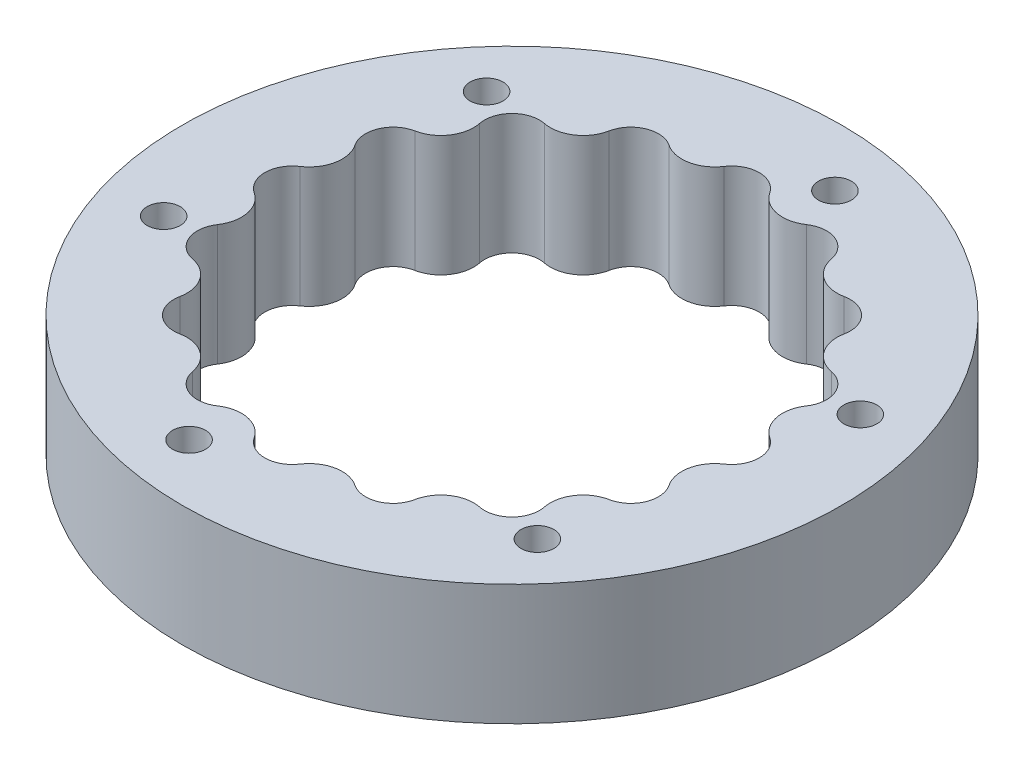
SolidWorks part; units mm, degrees
ref_plane "Front Plane" through (0, 0, 0) normal (0, 0, 1) x (1, 0, 0)
ref_plane "Top Plane" through (0, 0, 0) normal (0, 1, 0) x (1, 0, 0)
ref_plane "Right Plane" through (0, 0, 0) normal (1, 0, 0) x (0, 0, -1)
sketch "Sketch1" plane through (0, 0, 0) normal (0, 1, 0) x (1, 0, 0)
  arc A0 (-31.5919, 24.5347) -> (-34.7568, 19.7981) centre (0, 0) ccw
  arc A1 (4.9902, 39.6875) -> (-4.9902, 39.6875) centre (0, 40) ccw
  arc A2 (19.7981, 34.7568) -> (10.5774, 38.5761) centre (15.3073, 36.9552) ccw
  arc A3 (-31.5919, 24.5347) -> (-34.7568, 19.7981) centre (0, 0) ccw construction
  arc A4 (31.5919, 24.5347) -> (24.5347, 31.5919) centre (28.2843, 28.2843) ccw
  arc A5 (-31.5919, 24.5347) -> (-34.7568, 19.7981) centre (0, 0) ccw construction
  arc A6 (38.5761, 10.5774) -> (34.7568, 19.7981) centre (36.9552, 15.3073) ccw
  arc A7 (-31.5919, 24.5347) -> (-34.7568, 19.7981) centre (0, 0) ccw construction
  arc A8 (39.6875, -4.9902) -> (39.6875, 4.9902) centre (40, 0) ccw
  arc A9 (-31.5919, 24.5347) -> (-34.7568, 19.7981) centre (0, 0) ccw construction
  arc A10 (34.7568, -19.7981) -> (38.5761, -10.5774) centre (36.9552, -15.3073) ccw
  arc A11 (-31.5919, 24.5347) -> (-34.7568, 19.7981) centre (0, 0) ccw construction
  arc A12 (24.5347, -31.5919) -> (31.5919, -24.5347) centre (28.2843, -28.2843) ccw
  arc A13 (-31.5919, 24.5347) -> (-34.7568, 19.7981) centre (0, 0) ccw construction
  arc A14 (10.5774, -38.5761) -> (19.7981, -34.7568) centre (15.3073, -36.9552) ccw
  arc A15 (-31.5919, 24.5347) -> (-34.7568, 19.7981) centre (0, 0) ccw construction
  arc A16 (-4.9902, -39.6875) -> (4.9902, -39.6875) centre (0, -40) ccw
  arc A17 (-31.5919, 24.5347) -> (-34.7568, 19.7981) centre (0, 0) ccw construction
  arc A18 (-19.7981, -34.7568) -> (-10.5774, -38.5761) centre (-15.3073, -36.9552) ccw
  arc A19 (-31.5919, 24.5347) -> (-34.7568, 19.7981) centre (0, 0) ccw construction
  arc A20 (-31.5919, -24.5347) -> (-24.5347, -31.5919) centre (-28.2843, -28.2843) ccw
  arc A21 (-31.5919, 24.5347) -> (-34.7568, 19.7981) centre (0, 0) ccw construction
  arc A22 (-38.5761, -10.5774) -> (-34.7568, -19.7981) centre (-36.9552, -15.3073) ccw
  arc A23 (-31.5919, 24.5347) -> (-34.7568, 19.7981) centre (0, 0) ccw construction
  arc A24 (-39.6875, 4.9902) -> (-39.6875, -4.9902) centre (-40, 0) ccw
  arc A25 (-31.5919, 24.5347) -> (-34.7568, 19.7981) centre (0, 0) ccw construction
  arc A26 (-34.7568, 19.7981) -> (-38.5761, 10.5774) centre (-36.9552, 15.3073) ccw
  arc A27 (-31.5919, 24.5347) -> (-34.7568, 19.7981) centre (0, 0) ccw construction
  arc A28 (-24.5347, 31.5919) -> (-31.5919, 24.5347) centre (-28.2843, 28.2843) ccw
  arc A29 (-31.5919, 24.5347) -> (-34.7568, 19.7981) centre (0, 0) ccw construction
  arc A30 (-10.5774, 38.5761) -> (-19.7981, 34.7568) centre (-15.3073, 36.9552) ccw
  arc A31 (-31.5919, 24.5347) -> (-34.7568, 19.7981) centre (0, 0) ccw construction
  circle A32 centre (0, 0) radius 60
  arc A33 (-19.7981, 34.7568) -> (-24.5347, 31.5919) centre (0, 0) ccw
  arc A34 (-19.7981, 34.7568) -> (-24.5347, 31.5919) centre (0, 0) ccw construction
  arc A35 (-19.7981, 34.7568) -> (-24.5347, 31.5919) centre (0, 0) ccw construction
  arc A36 (-19.7981, 34.7568) -> (-24.5347, 31.5919) centre (0, 0) ccw construction
  arc A37 (-19.7981, 34.7568) -> (-24.5347, 31.5919) centre (0, 0) ccw construction
  arc A38 (-19.7981, 34.7568) -> (-24.5347, 31.5919) centre (0, 0) ccw construction
  arc A39 (-19.7981, 34.7568) -> (-24.5347, 31.5919) centre (0, 0) ccw construction
  arc A40 (-19.7981, 34.7568) -> (-24.5347, 31.5919) centre (0, 0) ccw construction
  arc A41 (-19.7981, 34.7568) -> (-24.5347, 31.5919) centre (0, 0) ccw construction
  arc A42 (-19.7981, 34.7568) -> (-24.5347, 31.5919) centre (0, 0) ccw construction
  arc A43 (-19.7981, 34.7568) -> (-24.5347, 31.5919) centre (0, 0) ccw construction
  arc A44 (-19.7981, 34.7568) -> (-24.5347, 31.5919) centre (0, 0) ccw construction
  arc A45 (-19.7981, 34.7568) -> (-24.5347, 31.5919) centre (0, 0) ccw construction
  arc A46 (-19.7981, 34.7568) -> (-24.5347, 31.5919) centre (0, 0) ccw construction
  arc A47 (-19.7981, 34.7568) -> (-24.5347, 31.5919) centre (0, 0) ccw construction
  arc A48 (-19.7981, 34.7568) -> (-24.5347, 31.5919) centre (0, 0) ccw construction
  arc A49 (-4.9902, 39.6875) -> (-10.5774, 38.5761) centre (0, 0) ccw
  arc A50 (-4.9902, 39.6875) -> (-10.5774, 38.5761) centre (0, 0) ccw construction
  arc A51 (-4.9902, 39.6875) -> (-10.5774, 38.5761) centre (0, 0) ccw construction
  arc A52 (-4.9902, 39.6875) -> (-10.5774, 38.5761) centre (0, 0) ccw construction
  arc A53 (-4.9902, 39.6875) -> (-10.5774, 38.5761) centre (0, 0) ccw construction
  arc A54 (-4.9902, 39.6875) -> (-10.5774, 38.5761) centre (0, 0) ccw construction
  arc A55 (-4.9902, 39.6875) -> (-10.5774, 38.5761) centre (0, 0) ccw construction
  arc A56 (-4.9902, 39.6875) -> (-10.5774, 38.5761) centre (0, 0) ccw construction
  arc A57 (-4.9902, 39.6875) -> (-10.5774, 38.5761) centre (0, 0) ccw construction
  arc A58 (-4.9902, 39.6875) -> (-10.5774, 38.5761) centre (0, 0) ccw construction
  arc A59 (-4.9902, 39.6875) -> (-10.5774, 38.5761) centre (0, 0) ccw construction
  arc A60 (-4.9902, 39.6875) -> (-10.5774, 38.5761) centre (0, 0) ccw construction
  arc A61 (-4.9902, 39.6875) -> (-10.5774, 38.5761) centre (0, 0) ccw construction
  arc A62 (-4.9902, 39.6875) -> (-10.5774, 38.5761) centre (0, 0) ccw construction
  arc A63 (-4.9902, 39.6875) -> (-10.5774, 38.5761) centre (0, 0) ccw construction
  arc A64 (-4.9902, 39.6875) -> (-10.5774, 38.5761) centre (0, 0) ccw construction
  arc A65 (10.5774, 38.5761) -> (4.9902, 39.6875) centre (0, 0) ccw
  arc A66 (10.5774, 38.5761) -> (4.9902, 39.6875) centre (0, 0) ccw construction
  arc A67 (10.5774, 38.5761) -> (4.9902, 39.6875) centre (0, 0) ccw construction
  arc A68 (10.5774, 38.5761) -> (4.9902, 39.6875) centre (0, 0) ccw construction
  arc A69 (10.5774, 38.5761) -> (4.9902, 39.6875) centre (0, 0) ccw construction
  arc A70 (10.5774, 38.5761) -> (4.9902, 39.6875) centre (0, 0) ccw construction
  arc A71 (10.5774, 38.5761) -> (4.9902, 39.6875) centre (0, 0) ccw construction
  arc A72 (10.5774, 38.5761) -> (4.9902, 39.6875) centre (0, 0) ccw construction
  arc A73 (10.5774, 38.5761) -> (4.9902, 39.6875) centre (0, 0) ccw construction
  arc A74 (10.5774, 38.5761) -> (4.9902, 39.6875) centre (0, 0) ccw construction
  arc A75 (10.5774, 38.5761) -> (4.9902, 39.6875) centre (0, 0) ccw construction
  arc A76 (10.5774, 38.5761) -> (4.9902, 39.6875) centre (0, 0) ccw construction
  arc A77 (10.5774, 38.5761) -> (4.9902, 39.6875) centre (0, 0) ccw construction
  arc A78 (10.5774, 38.5761) -> (4.9902, 39.6875) centre (0, 0) ccw construction
  arc A79 (10.5774, 38.5761) -> (4.9902, 39.6875) centre (0, 0) ccw construction
  arc A80 (10.5774, 38.5761) -> (4.9902, 39.6875) centre (0, 0) ccw construction
  arc A81 (24.5347, 31.5919) -> (19.7981, 34.7568) centre (0, 0) ccw
  arc A82 (24.5347, 31.5919) -> (19.7981, 34.7568) centre (0, 0) ccw construction
  arc A83 (24.5347, 31.5919) -> (19.7981, 34.7568) centre (0, 0) ccw construction
  arc A84 (24.5347, 31.5919) -> (19.7981, 34.7568) centre (0, 0) ccw construction
  arc A85 (24.5347, 31.5919) -> (19.7981, 34.7568) centre (0, 0) ccw construction
  arc A86 (24.5347, 31.5919) -> (19.7981, 34.7568) centre (0, 0) ccw construction
  arc A87 (24.5347, 31.5919) -> (19.7981, 34.7568) centre (0, 0) ccw construction
  arc A88 (24.5347, 31.5919) -> (19.7981, 34.7568) centre (0, 0) ccw construction
  arc A89 (24.5347, 31.5919) -> (19.7981, 34.7568) centre (0, 0) ccw construction
  arc A90 (24.5347, 31.5919) -> (19.7981, 34.7568) centre (0, 0) ccw construction
  arc A91 (24.5347, 31.5919) -> (19.7981, 34.7568) centre (0, 0) ccw construction
  arc A92 (24.5347, 31.5919) -> (19.7981, 34.7568) centre (0, 0) ccw construction
  arc A93 (24.5347, 31.5919) -> (19.7981, 34.7568) centre (0, 0) ccw construction
  arc A94 (24.5347, 31.5919) -> (19.7981, 34.7568) centre (0, 0) ccw construction
  arc A95 (24.5347, 31.5919) -> (19.7981, 34.7568) centre (0, 0) ccw construction
  arc A96 (24.5347, 31.5919) -> (19.7981, 34.7568) centre (0, 0) ccw construction
  arc A97 (34.7568, 19.7981) -> (31.5919, 24.5347) centre (0, 0) ccw
  arc A98 (34.7568, 19.7981) -> (31.5919, 24.5347) centre (0, 0) ccw construction
  arc A99 (34.7568, 19.7981) -> (31.5919, 24.5347) centre (0, 0) ccw construction
  arc A100 (34.7568, 19.7981) -> (31.5919, 24.5347) centre (0, 0) ccw construction
  arc A101 (34.7568, 19.7981) -> (31.5919, 24.5347) centre (0, 0) ccw construction
  arc A102 (34.7568, 19.7981) -> (31.5919, 24.5347) centre (0, 0) ccw construction
  arc A103 (34.7568, 19.7981) -> (31.5919, 24.5347) centre (0, 0) ccw construction
  arc A104 (34.7568, 19.7981) -> (31.5919, 24.5347) centre (0, 0) ccw construction
  arc A105 (34.7568, 19.7981) -> (31.5919, 24.5347) centre (0, 0) ccw construction
  arc A106 (34.7568, 19.7981) -> (31.5919, 24.5347) centre (0, 0) ccw construction
  arc A107 (34.7568, 19.7981) -> (31.5919, 24.5347) centre (0, 0) ccw construction
  arc A108 (34.7568, 19.7981) -> (31.5919, 24.5347) centre (0, 0) ccw construction
  arc A109 (34.7568, 19.7981) -> (31.5919, 24.5347) centre (0, 0) ccw construction
  arc A110 (34.7568, 19.7981) -> (31.5919, 24.5347) centre (0, 0) ccw construction
  arc A111 (34.7568, 19.7981) -> (31.5919, 24.5347) centre (0, 0) ccw construction
  arc A112 (34.7568, 19.7981) -> (31.5919, 24.5347) centre (0, 0) ccw construction
  arc A113 (39.6875, 4.9902) -> (38.5761, 10.5774) centre (0, 0) ccw
  arc A114 (39.6875, 4.9902) -> (38.5761, 10.5774) centre (0, 0) ccw construction
  arc A115 (39.6875, 4.9902) -> (38.5761, 10.5774) centre (0, 0) ccw construction
  arc A116 (39.6875, 4.9902) -> (38.5761, 10.5774) centre (0, 0) ccw construction
  arc A117 (39.6875, 4.9902) -> (38.5761, 10.5774) centre (0, 0) ccw construction
  arc A118 (39.6875, 4.9902) -> (38.5761, 10.5774) centre (0, 0) ccw construction
  arc A119 (39.6875, 4.9902) -> (38.5761, 10.5774) centre (0, 0) ccw construction
  arc A120 (39.6875, 4.9902) -> (38.5761, 10.5774) centre (0, 0) ccw construction
  arc A121 (39.6875, 4.9902) -> (38.5761, 10.5774) centre (0, 0) ccw construction
  arc A122 (39.6875, 4.9902) -> (38.5761, 10.5774) centre (0, 0) ccw construction
  arc A123 (39.6875, 4.9902) -> (38.5761, 10.5774) centre (0, 0) ccw construction
  arc A124 (39.6875, 4.9902) -> (38.5761, 10.5774) centre (0, 0) ccw construction
  arc A125 (39.6875, 4.9902) -> (38.5761, 10.5774) centre (0, 0) ccw construction
  arc A126 (39.6875, 4.9902) -> (38.5761, 10.5774) centre (0, 0) ccw construction
  arc A127 (39.6875, 4.9902) -> (38.5761, 10.5774) centre (0, 0) ccw construction
  arc A128 (39.6875, 4.9902) -> (38.5761, 10.5774) centre (0, 0) ccw construction
  arc A129 (38.5761, -10.5774) -> (39.6875, -4.9902) centre (0, 0) ccw
  arc A130 (38.5761, -10.5774) -> (39.6875, -4.9902) centre (0, 0) ccw construction
  arc A131 (38.5761, -10.5774) -> (39.6875, -4.9902) centre (0, 0) ccw construction
  arc A132 (38.5761, -10.5774) -> (39.6875, -4.9902) centre (0, 0) ccw construction
  arc A133 (38.5761, -10.5774) -> (39.6875, -4.9902) centre (0, 0) ccw construction
  arc A134 (38.5761, -10.5774) -> (39.6875, -4.9902) centre (0, 0) ccw construction
  arc A135 (38.5761, -10.5774) -> (39.6875, -4.9902) centre (0, 0) ccw construction
  arc A136 (38.5761, -10.5774) -> (39.6875, -4.9902) centre (0, 0) ccw construction
  arc A137 (38.5761, -10.5774) -> (39.6875, -4.9902) centre (0, 0) ccw construction
  arc A138 (38.5761, -10.5774) -> (39.6875, -4.9902) centre (0, 0) ccw construction
  arc A139 (38.5761, -10.5774) -> (39.6875, -4.9902) centre (0, 0) ccw construction
  arc A140 (38.5761, -10.5774) -> (39.6875, -4.9902) centre (0, 0) ccw construction
  arc A141 (38.5761, -10.5774) -> (39.6875, -4.9902) centre (0, 0) ccw construction
  arc A142 (38.5761, -10.5774) -> (39.6875, -4.9902) centre (0, 0) ccw construction
  arc A143 (38.5761, -10.5774) -> (39.6875, -4.9902) centre (0, 0) ccw construction
  arc A144 (38.5761, -10.5774) -> (39.6875, -4.9902) centre (0, 0) ccw construction
  arc A145 (31.5919, -24.5347) -> (34.7568, -19.7981) centre (0, 0) ccw
  arc A146 (31.5919, -24.5347) -> (34.7568, -19.7981) centre (0, 0) ccw construction
  arc A147 (31.5919, -24.5347) -> (34.7568, -19.7981) centre (0, 0) ccw construction
  arc A148 (31.5919, -24.5347) -> (34.7568, -19.7981) centre (0, 0) ccw construction
  arc A149 (31.5919, -24.5347) -> (34.7568, -19.7981) centre (0, 0) ccw construction
  arc A150 (31.5919, -24.5347) -> (34.7568, -19.7981) centre (0, 0) ccw construction
  arc A151 (31.5919, -24.5347) -> (34.7568, -19.7981) centre (0, 0) ccw construction
  arc A152 (31.5919, -24.5347) -> (34.7568, -19.7981) centre (0, 0) ccw construction
  arc A153 (31.5919, -24.5347) -> (34.7568, -19.7981) centre (0, 0) ccw construction
  arc A154 (31.5919, -24.5347) -> (34.7568, -19.7981) centre (0, 0) ccw construction
  arc A155 (31.5919, -24.5347) -> (34.7568, -19.7981) centre (0, 0) ccw construction
  arc A156 (31.5919, -24.5347) -> (34.7568, -19.7981) centre (0, 0) ccw construction
  arc A157 (31.5919, -24.5347) -> (34.7568, -19.7981) centre (0, 0) ccw construction
  arc A158 (31.5919, -24.5347) -> (34.7568, -19.7981) centre (0, 0) ccw construction
  arc A159 (31.5919, -24.5347) -> (34.7568, -19.7981) centre (0, 0) ccw construction
  arc A160 (31.5919, -24.5347) -> (34.7568, -19.7981) centre (0, 0) ccw construction
  arc A161 (19.7981, -34.7568) -> (24.5347, -31.5919) centre (0, 0) ccw
  arc A162 (19.7981, -34.7568) -> (24.5347, -31.5919) centre (0, 0) ccw construction
  arc A163 (19.7981, -34.7568) -> (24.5347, -31.5919) centre (0, 0) ccw construction
  arc A164 (19.7981, -34.7568) -> (24.5347, -31.5919) centre (0, 0) ccw construction
  arc A165 (19.7981, -34.7568) -> (24.5347, -31.5919) centre (0, 0) ccw construction
  arc A166 (19.7981, -34.7568) -> (24.5347, -31.5919) centre (0, 0) ccw construction
  arc A167 (19.7981, -34.7568) -> (24.5347, -31.5919) centre (0, 0) ccw construction
  arc A168 (19.7981, -34.7568) -> (24.5347, -31.5919) centre (0, 0) ccw construction
  arc A169 (19.7981, -34.7568) -> (24.5347, -31.5919) centre (0, 0) ccw construction
  arc A170 (19.7981, -34.7568) -> (24.5347, -31.5919) centre (0, 0) ccw construction
  arc A171 (19.7981, -34.7568) -> (24.5347, -31.5919) centre (0, 0) ccw construction
  arc A172 (19.7981, -34.7568) -> (24.5347, -31.5919) centre (0, 0) ccw construction
  arc A173 (19.7981, -34.7568) -> (24.5347, -31.5919) centre (0, 0) ccw construction
  arc A174 (19.7981, -34.7568) -> (24.5347, -31.5919) centre (0, 0) ccw construction
  arc A175 (19.7981, -34.7568) -> (24.5347, -31.5919) centre (0, 0) ccw construction
  arc A176 (19.7981, -34.7568) -> (24.5347, -31.5919) centre (0, 0) ccw construction
  arc A177 (4.9902, -39.6875) -> (10.5774, -38.5761) centre (0, 0) ccw
  arc A178 (4.9902, -39.6875) -> (10.5774, -38.5761) centre (0, 0) ccw construction
  arc A179 (4.9902, -39.6875) -> (10.5774, -38.5761) centre (0, 0) ccw construction
  arc A180 (4.9902, -39.6875) -> (10.5774, -38.5761) centre (0, 0) ccw construction
  arc A181 (4.9902, -39.6875) -> (10.5774, -38.5761) centre (0, 0) ccw construction
  arc A182 (4.9902, -39.6875) -> (10.5774, -38.5761) centre (0, 0) ccw construction
  arc A183 (4.9902, -39.6875) -> (10.5774, -38.5761) centre (0, 0) ccw construction
  arc A184 (4.9902, -39.6875) -> (10.5774, -38.5761) centre (0, 0) ccw construction
  arc A185 (4.9902, -39.6875) -> (10.5774, -38.5761) centre (0, 0) ccw construction
  arc A186 (4.9902, -39.6875) -> (10.5774, -38.5761) centre (0, 0) ccw construction
  arc A187 (4.9902, -39.6875) -> (10.5774, -38.5761) centre (0, 0) ccw construction
  arc A188 (4.9902, -39.6875) -> (10.5774, -38.5761) centre (0, 0) ccw construction
  arc A189 (4.9902, -39.6875) -> (10.5774, -38.5761) centre (0, 0) ccw construction
  arc A190 (4.9902, -39.6875) -> (10.5774, -38.5761) centre (0, 0) ccw construction
  arc A191 (4.9902, -39.6875) -> (10.5774, -38.5761) centre (0, 0) ccw construction
  arc A192 (4.9902, -39.6875) -> (10.5774, -38.5761) centre (0, 0) ccw construction
  arc A193 (-10.5774, -38.5761) -> (-4.9902, -39.6875) centre (0, 0) ccw
  arc A194 (-10.5774, -38.5761) -> (-4.9902, -39.6875) centre (0, 0) ccw construction
  arc A195 (-10.5774, -38.5761) -> (-4.9902, -39.6875) centre (0, 0) ccw construction
  arc A196 (-10.5774, -38.5761) -> (-4.9902, -39.6875) centre (0, 0) ccw construction
  arc A197 (-10.5774, -38.5761) -> (-4.9902, -39.6875) centre (0, 0) ccw construction
  arc A198 (-10.5774, -38.5761) -> (-4.9902, -39.6875) centre (0, 0) ccw construction
  arc A199 (-10.5774, -38.5761) -> (-4.9902, -39.6875) centre (0, 0) ccw construction
  arc A200 (-10.5774, -38.5761) -> (-4.9902, -39.6875) centre (0, 0) ccw construction
  arc A201 (-10.5774, -38.5761) -> (-4.9902, -39.6875) centre (0, 0) ccw construction
  arc A202 (-10.5774, -38.5761) -> (-4.9902, -39.6875) centre (0, 0) ccw construction
  arc A203 (-10.5774, -38.5761) -> (-4.9902, -39.6875) centre (0, 0) ccw construction
  arc A204 (-10.5774, -38.5761) -> (-4.9902, -39.6875) centre (0, 0) ccw construction
  arc A205 (-10.5774, -38.5761) -> (-4.9902, -39.6875) centre (0, 0) ccw construction
  arc A206 (-10.5774, -38.5761) -> (-4.9902, -39.6875) centre (0, 0) ccw construction
  arc A207 (-10.5774, -38.5761) -> (-4.9902, -39.6875) centre (0, 0) ccw construction
  arc A208 (-10.5774, -38.5761) -> (-4.9902, -39.6875) centre (0, 0) ccw construction
  arc A209 (-24.5347, -31.5919) -> (-19.7981, -34.7568) centre (0, 0) ccw
  arc A210 (-24.5347, -31.5919) -> (-19.7981, -34.7568) centre (0, 0) ccw construction
  arc A211 (-24.5347, -31.5919) -> (-19.7981, -34.7568) centre (0, 0) ccw construction
  arc A212 (-24.5347, -31.5919) -> (-19.7981, -34.7568) centre (0, 0) ccw construction
  arc A213 (-24.5347, -31.5919) -> (-19.7981, -34.7568) centre (0, 0) ccw construction
  arc A214 (-24.5347, -31.5919) -> (-19.7981, -34.7568) centre (0, 0) ccw construction
  arc A215 (-24.5347, -31.5919) -> (-19.7981, -34.7568) centre (0, 0) ccw construction
  arc A216 (-24.5347, -31.5919) -> (-19.7981, -34.7568) centre (0, 0) ccw construction
  arc A217 (-24.5347, -31.5919) -> (-19.7981, -34.7568) centre (0, 0) ccw construction
  arc A218 (-24.5347, -31.5919) -> (-19.7981, -34.7568) centre (0, 0) ccw construction
  arc A219 (-24.5347, -31.5919) -> (-19.7981, -34.7568) centre (0, 0) ccw construction
  arc A220 (-24.5347, -31.5919) -> (-19.7981, -34.7568) centre (0, 0) ccw construction
  arc A221 (-24.5347, -31.5919) -> (-19.7981, -34.7568) centre (0, 0) ccw construction
  arc A222 (-24.5347, -31.5919) -> (-19.7981, -34.7568) centre (0, 0) ccw construction
  arc A223 (-24.5347, -31.5919) -> (-19.7981, -34.7568) centre (0, 0) ccw construction
  arc A224 (-24.5347, -31.5919) -> (-19.7981, -34.7568) centre (0, 0) ccw construction
  arc A225 (-34.7568, -19.7981) -> (-31.5919, -24.5347) centre (0, 0) ccw
  arc A226 (-34.7568, -19.7981) -> (-31.5919, -24.5347) centre (0, 0) ccw construction
  arc A227 (-34.7568, -19.7981) -> (-31.5919, -24.5347) centre (0, 0) ccw construction
  arc A228 (-34.7568, -19.7981) -> (-31.5919, -24.5347) centre (0, 0) ccw construction
  arc A229 (-34.7568, -19.7981) -> (-31.5919, -24.5347) centre (0, 0) ccw construction
  arc A230 (-34.7568, -19.7981) -> (-31.5919, -24.5347) centre (0, 0) ccw construction
  arc A231 (-34.7568, -19.7981) -> (-31.5919, -24.5347) centre (0, 0) ccw construction
  arc A232 (-34.7568, -19.7981) -> (-31.5919, -24.5347) centre (0, 0) ccw construction
  arc A233 (-34.7568, -19.7981) -> (-31.5919, -24.5347) centre (0, 0) ccw construction
  arc A234 (-34.7568, -19.7981) -> (-31.5919, -24.5347) centre (0, 0) ccw construction
  arc A235 (-34.7568, -19.7981) -> (-31.5919, -24.5347) centre (0, 0) ccw construction
  arc A236 (-34.7568, -19.7981) -> (-31.5919, -24.5347) centre (0, 0) ccw construction
  arc A237 (-34.7568, -19.7981) -> (-31.5919, -24.5347) centre (0, 0) ccw construction
  arc A238 (-34.7568, -19.7981) -> (-31.5919, -24.5347) centre (0, 0) ccw construction
  arc A239 (-34.7568, -19.7981) -> (-31.5919, -24.5347) centre (0, 0) ccw construction
  arc A240 (-34.7568, -19.7981) -> (-31.5919, -24.5347) centre (0, 0) ccw construction
  arc A241 (-39.6875, -4.9902) -> (-38.5761, -10.5774) centre (0, 0) ccw
  arc A242 (-39.6875, -4.9902) -> (-38.5761, -10.5774) centre (0, 0) ccw construction
  arc A243 (-39.6875, -4.9902) -> (-38.5761, -10.5774) centre (0, 0) ccw construction
  arc A244 (-39.6875, -4.9902) -> (-38.5761, -10.5774) centre (0, 0) ccw construction
  arc A245 (-39.6875, -4.9902) -> (-38.5761, -10.5774) centre (0, 0) ccw construction
  arc A246 (-39.6875, -4.9902) -> (-38.5761, -10.5774) centre (0, 0) ccw construction
  arc A247 (-39.6875, -4.9902) -> (-38.5761, -10.5774) centre (0, 0) ccw construction
  arc A248 (-39.6875, -4.9902) -> (-38.5761, -10.5774) centre (0, 0) ccw construction
  arc A249 (-39.6875, -4.9902) -> (-38.5761, -10.5774) centre (0, 0) ccw construction
  arc A250 (-39.6875, -4.9902) -> (-38.5761, -10.5774) centre (0, 0) ccw construction
  arc A251 (-39.6875, -4.9902) -> (-38.5761, -10.5774) centre (0, 0) ccw construction
  arc A252 (-39.6875, -4.9902) -> (-38.5761, -10.5774) centre (0, 0) ccw construction
  arc A253 (-39.6875, -4.9902) -> (-38.5761, -10.5774) centre (0, 0) ccw construction
  arc A254 (-39.6875, -4.9902) -> (-38.5761, -10.5774) centre (0, 0) ccw construction
  arc A255 (-39.6875, -4.9902) -> (-38.5761, -10.5774) centre (0, 0) ccw construction
  arc A256 (-39.6875, -4.9902) -> (-38.5761, -10.5774) centre (0, 0) ccw construction
  arc A257 (-38.5761, 10.5774) -> (-39.6875, 4.9902) centre (0, 0) ccw
  arc A258 (-38.5761, 10.5774) -> (-39.6875, 4.9902) centre (0, 0) ccw construction
  arc A259 (-38.5761, 10.5774) -> (-39.6875, 4.9902) centre (0, 0) ccw construction
  arc A260 (-38.5761, 10.5774) -> (-39.6875, 4.9902) centre (0, 0) ccw construction
  arc A261 (-38.5761, 10.5774) -> (-39.6875, 4.9902) centre (0, 0) ccw construction
  arc A262 (-38.5761, 10.5774) -> (-39.6875, 4.9902) centre (0, 0) ccw construction
  arc A263 (-38.5761, 10.5774) -> (-39.6875, 4.9902) centre (0, 0) ccw construction
  arc A264 (-38.5761, 10.5774) -> (-39.6875, 4.9902) centre (0, 0) ccw construction
  arc A265 (-38.5761, 10.5774) -> (-39.6875, 4.9902) centre (0, 0) ccw construction
  arc A266 (-38.5761, 10.5774) -> (-39.6875, 4.9902) centre (0, 0) ccw construction
  arc A267 (-38.5761, 10.5774) -> (-39.6875, 4.9902) centre (0, 0) ccw construction
  arc A268 (-38.5761, 10.5774) -> (-39.6875, 4.9902) centre (0, 0) ccw construction
  arc A269 (-38.5761, 10.5774) -> (-39.6875, 4.9902) centre (0, 0) ccw construction
  arc A270 (-38.5761, 10.5774) -> (-39.6875, 4.9902) centre (0, 0) ccw construction
  arc A271 (-38.5761, 10.5774) -> (-39.6875, 4.9902) centre (0, 0) ccw construction
  arc A272 (-38.5761, 10.5774) -> (-39.6875, 4.9902) centre (0, 0) ccw construction
  point P52 (0, 0)
  dimension "D1" = 80
  dimension "D2" = 10
  dimension "D4" = 120
  dimension "D3" = 16
extrude "Boss-Extrude1" add sketch "Sketch1" along normal blind 22
fillet "Fillet1" radius 5 32 edges at (-31.5919, 11, -24.5347) (-34.7568, 11, -19.7981) (10.5774, 11, 38.5761) (4.9902, 11, 39.6875) (-4.9902, 11, 39.6875) (-10.5774, 11, 38.5761) (-19.7981, 11, 34.7568) (-24.5347, 11, 31.5919) (-31.5919, 11, 24.5347) (-34.7568, 11, 19.7981) (-38.5761, 11, 10.5774) (-39.6875, 11, 4.9902) (-39.6875, 11, -4.9902) (-38.5761, 11, -10.5774) (19.7981, 11, 34.7568) (24.5347, 11, 31.5919) (31.5919, 11, 24.5347) (34.7568, 11, 19.7981) (38.5761, 11, 10.5774) (39.6875, 11, 4.9902) (39.6875, 11, -4.9902) (38.5761, 11, -10.5774) (34.7568, 11, -19.7981) (31.5919, 11, -24.5347) (24.5347, 11, -31.5919) (19.7981, 11, -34.7568) (10.5774, 11, -38.5761) (4.9902, 11, -39.6875) (-4.9902, 11, -39.6875) (-10.5774, 11, -38.5761) (-19.7981, 11, -34.7568) (-24.5347, 11, -31.5919)
fillet "Fillet2" radius 6 16 edges at (-7.8059, 11, 39.2431) (7.8059, 11, 39.2431) (22.2294, 11, 33.2687) (33.2687, 11, 22.2294) (-22.2294, 11, 33.2687) (-33.2687, 11, 22.2294) (-39.2431, 11, 7.8059) (-39.2431, 11, -7.8059) (39.2431, 11, 7.8059) (39.2431, 11, -7.8059) (33.2687, 11, -22.2294) (22.2294, 11, -33.2687) (7.8059, 11, -39.2431) (-7.8059, 11, -39.2431) (-22.2294, 11, -33.2687) (-33.2687, 11, -22.2294)
sketch "Sketch3" plane through (0, 22, 0) normal (0, 1, 0) x (1, 0, 0)
  line L0 (7.9956, 40.1966) -> (11.7054, 58.8471) construction
  circle A0 centre (0, 0) radius 50 construction
  circle A4 centre (9.7545, 49.0393) radius 3
  arc A5 (4.1664, 42.7642) -> (12.5159, 41.1034) centre (9.1661, 46.0813) ccw construction
  circle A6 centre (0, 0) radius 60 construction
  circle A7 centre (47.3465, 16.072) radius 3
  circle A8 centre (37.592, -32.9673) radius 3
  circle A9 centre (-9.7545, -49.0393) radius 3
  circle A10 centre (-47.3465, -16.072) radius 3
  circle A11 centre (-37.592, 32.9673) radius 3
  point P13 (9.1661, 46.0813)
  point P31 (0, 0)
  dimension "D1" = 100
  dimension "D2" = 6
  dimension "D3" = 6
extrude "Cut-Extrude1" cut sketch "Sketch3" against normal through all
ref_axis "Axis1" [suppressed] through (37.592, 0, 32.9673) along (0, 1, 0)
ref_axis "Axis2" [suppressed] through (-9.7545, 0, 49.0393) along (0, 1, 0)
ref_plane "Plane1" [suppressed] through (13.9187, 0, 41.0033) normal (-0.3214, 0, -0.9469) x (-0.9469, 0, 0.3214)
ref_plane "Plane2" [suppressed] through (19.2864, 0, 56.8158) normal (0.3214, 0, 0.9469) x (0.9469, 0, -0.3214)
ref_plane "Plane3" [suppressed] through (19.9292, 0, 58.7097) normal (0.3214, 0, 0.9469) x (0.9469, 0, -0.3214)
sketch "Sketch4" [suppressed] plane through (19.9292, 0, 58.7097) normal (0.3214, 0, 0.9469) x (0.9469, 0, -0.3214)
  circle A0 centre (0, 11) radius 4.5
  dimension "D1" = 9
  dimension "D2" = 11
extrude "Boss-Extrude2" [suppressed] add sketch "Sketch4" against normal up to next
sketch "Sketch5" [suppressed] plane through (19.9292, 0, 58.7097) normal (0.3214, 0, 0.9469) x (0.9469, 0, -0.3214)
  circle A0 centre (0, 11) radius 3.3
  dimension "D1" = 6.6
extrude "Cut-Extrude2" [suppressed] cut sketch "Sketch5" against normal blind 10.5
pattern_circular "CirPattern1" [suppressed] count 3 every 60 of bodies 104
chamfer "Chamfer1" [suppressed] distance 1 angle 45
equation "\"R_ROLL\"= 5mm"
equation "\"D_SUN\"= 80mm"
equation "\"NUM_ROLL\"= 16"
equation "\"RHO\"= 1mm"
equation "\"D_SHAFT\"= 15mm"
equation "\"D_OUTPUT\"= 40mm"
equation "\"NUM_OUT\"= 6"
equation "\"R_OUT_ROLL\"= 5mm"
equation "\"D1@Sketch1\"=\"D_SUN\""
equation "\"D2@Sketch1\"=\"R_ROLL\"*2"
equation "\"D3@Sketch1\"=\"NUM_ROLL\""
equation "\"D4@Sketch1\"=\"D_SUN\"+40"
